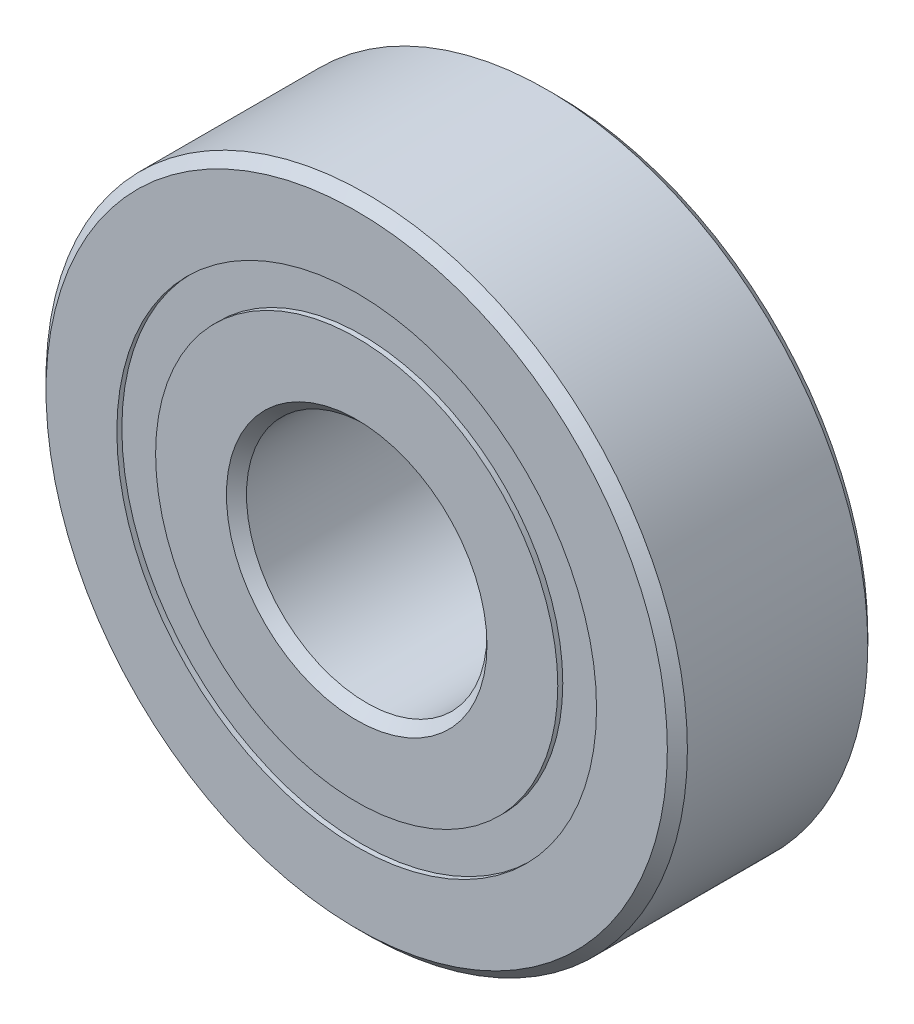
SolidWorks part; units mm, degrees
ref_plane "Front Plane" through (0, 0, 0) normal (0, 0, 1) x (1, 0, 0)
ref_plane "Top Plane" through (0, 0, 0) normal (0, 1, 0) x (1, 0, 0)
ref_plane "Right Plane" through (0, 0, 0) normal (1, 0, 0) x (0, 0, -1)
sketch "Sketch1" plane through (0, 0, 0) normal (1, 0, 0) x (0, 0, -1)
  line L0 (-5, 0) -> (5, 0) construction
  line L1 (0, 16) -> (0, -16) construction
  line L2 (4.5, 16) -> (-4.5, 16)
  line L3 (-4.5, 16) -> (-5, 15.5)
  line L4 (-5, 15.5) -> (-5, 11.967)
  line L5 (-5, 11.967) -> (-2.2222, 11.967)
  line L6 (5, 11.967) -> (2.2222, 11.967)
  line L7 (5, 15.5) -> (5, 11.967)
  line L8 (4.5, 16) -> (5, 15.5)
  line L9 (0, 16) -> (0, 11) construction
  line L10 (0, 11) -> (0, 6) construction
  arc A0 (-2.2222, 11.967) -> (2.2222, 11.967) centre (0, 11) cw
  point P14 (0, 6)
  dimension "Width" = 10
  dimension "OD" = 32
  dimension "D1" = 45
  dimension "D2" = 0.5
  dimension "Shaft Dia" = 12
  dimension "D3" = 4.4444
  dimension "D4" = 0.967
revolve "Revolve1" add sketch "Sketch1" angle 360 about L0
sketch "Sketch3" plane through (0, 0, 0) normal (1, 0, 0) x (0, 0, -1)
  line L0 (-5, 10.033) -> (-2.2222, 10.033)
  line L1 (0, 16) -> (0, -16) construction
  line L2 (-5, 15.5) -> (-5, 11.967) construction
  line L3 (-5, 10.033) -> (-5, 6.5)
  line L4 (-4.5, 16) -> (-5, 15.5) construction
  line L5 (-5, 6.5) -> (-4.5, 6)
  line L6 (-4.5, 6) -> (4.5, 6)
  line L7 (4.5, 16) -> (4.5, -16) construction
  line L8 (4.5, 6) -> (5, 6.5)
  line L9 (5, -15.5) -> (5, 15.5) construction
  line L10 (5, 6.5) -> (5, 10.033)
  line L11 (5, 10.033) -> (2.2222, 10.033)
  line L13 (4.5, 16) -> (5, 15.5) construction
  arc A0 (2.2222, 11.967) -> (-2.2222, 11.967) centre (0, 11) ccw construction
  arc A1 (2.2222, 10.033) -> (-2.2222, 10.033) centre (0, 11) cw
revolve "Revolve3" add sketch "Sketch3" angle 360 about L0
sketch "Sketch4" plane through (0, 0, 0) normal (1, 0, 0) x (0, 0, -1)
  line L0 (-2.4235, 11) -> (2.4235, 11)
  arc A2 (-2.4235, 11) -> (2.4235, 11) centre (0, 11) cw
  arc A3 (2.2222, 11.967) -> (-2.2222, 11.967) centre (0, 11) ccw construction
revolve "Revolve4" add sketch "Sketch4" angle 360 about L0
ref_axis "Axis1" through (0, 0, -5) along (0, 0, 1)
pattern_circular "CirPattern1" count 12 every 30 about axis through (0, 0, -5) along (0, 0, 1) of bodies 104
sketch "Sketch5" plane through (0, 0, 0) normal (1, 0, 0) x (0, 0, -1)
  line L0 (-5, 11.967) -> (-2.2222, 11.967) construction
  line L1 (-4.75, 11.967) -> (-2.4235, 11.967)
  line L2 (-4.75, 11.967) -> (-4.75, 10.033)
  line L3 (-4.75, 10.033) -> (-2.4235, 10.033)
  line L4 (-2.4235, 11.967) -> (-2.4235, 10.033)
  line L5 (-5, 10.033) -> (-2.2222, 10.033) construction
  line L6 (5, 11.967) -> (2.2222, 11.967) construction
  line L7 (4.75, 11.967) -> (2.4235, 11.967)
  line L8 (4.75, 11.967) -> (4.75, 10.033)
  line L9 (4.75, 10.033) -> (2.4235, 10.033)
  line L10 (2.4235, 11.967) -> (2.4235, 10.033)
  line L11 (5, 10.033) -> (2.2222, 10.033) construction
  line L12 (-4.5, 16) -> (-5, 15.5) construction
  point P18 (-4.75, 15.75)
revolve "Revolve5" add sketch "Sketch5" angle 360 about L0
equation "\"D2@Sketch1\" = \"Width@Sketch1\"*.05"
equation "\"D3@Sketch1\" = \"Width@Sketch1\"/2.25"
equation "\"D4@Sketch1\" = (((\"OD@Sketch1\"-\"Width@Sketch1\")/2)/3.25)/3.5"
equation "\"D2@CirPattern1\" = 360/\"Balls@CirPattern1\""
